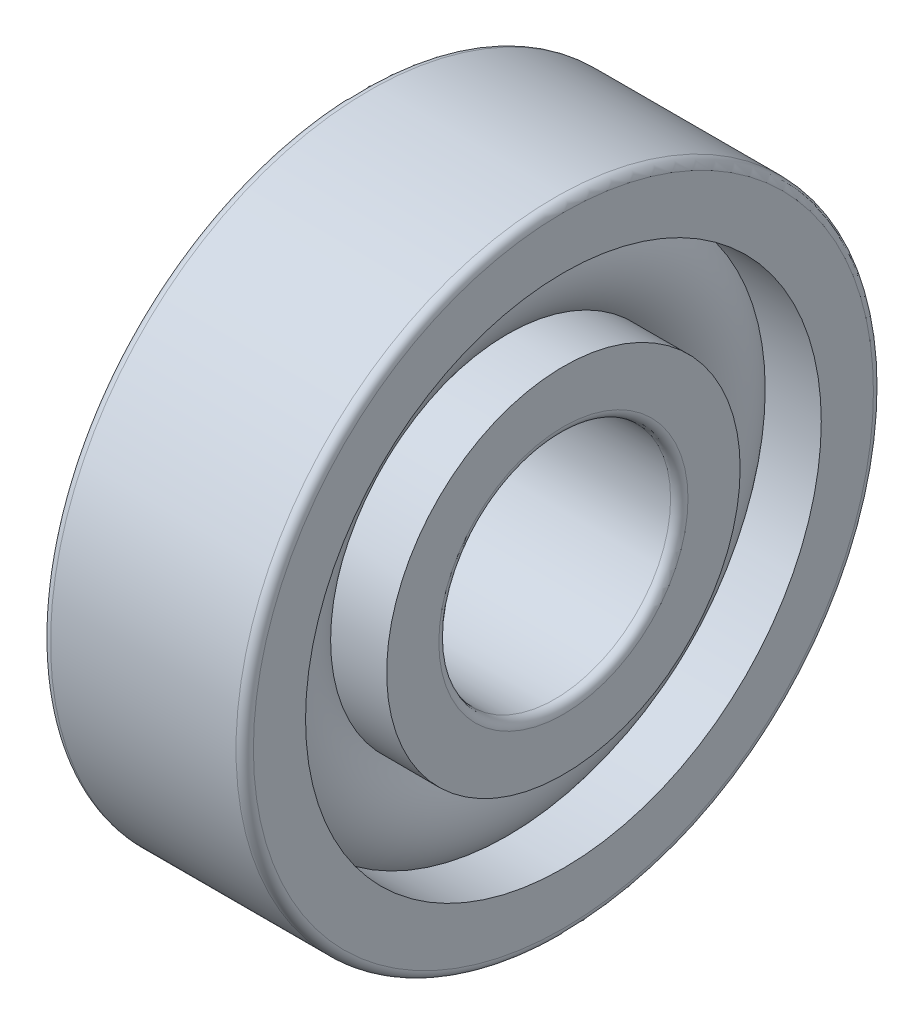
SolidWorks part; units mm, degrees
ref_plane "Plane1" through (0, 0, 0) normal (0, 0, 1) x (1, 0, 0)
ref_plane "Plane2" through (0, 0, 0) normal (0, 1, 0) x (1, 0, 0)
ref_plane "Plane3" through (0, 0, 0) normal (1, 0, 0) x (0, 0, -1)
other "Configuration Table"
sketch "Clipboard" plane through (0, 0, 0) normal (0, 0, 1) x (1, 0, 0)
  line L0 (-10, 0) -> (10, 0) construction
  line L1 (0, 0) -> (22.3471, -0.7804)
  line L2 (0, 0) -> (7.4954, 0.2617)
  line L3 (0, 0) -> (22.3471, -0.7804)
  line L4 (0, 0) -> (-22.3573, -0.3902)
  dimension "BallCLRad" = 7.5
  dimension "Count" = 2
sketch "CagSpiSke" plane through (0, 0, 0) normal (0, 0, 1) x (1, 0, 0)
  line L0 (0.21, 7.15) -> (0.21, 7.85)
  line L1 (0.21, 7.85) -> (-0.21, 7.85)
  line L2 (-0.21, 7.85) -> (-0.21, 7.15)
  line L3 (-0.21, 7.15) -> (0.21, 7.15)
  line L4 (-20.6375, 0) -> (20.6375, 0) construction
  line L5 (0, 0) -> (0, 23.7692) construction
  dimension "OD" = 15.7
  dimension "ID" = 14.3
revolve "CageSpine" add sketch "CagSpiSke" angle 0.001 about L4 reverse direction yes
ref_axis "Axis1" through (-50, 0, 0) along (1, 0, 0)
sketch "CagBalSke" plane through (0, 0, 0) normal (0, 0, 1) x (1, 0, 0)
  line L0 (-2.31, 7.5) -> (2.31, 7.5)
  line L1 (-1.905, 7.5) -> (1.905, 7.5) construction
  line L2 (-10, 0) -> (10, 0) construction
  line L3 (0, 0) -> (0, 24) construction
  arc A0 (2.31, 7.5) -> (-2.31, 7.5) centre (0, 7.5) cw
  dimension "BallCLRad" = 7.5
revolve "CageBall" [suppressed] add sketch "CagBalSke" angle 360 about L1 reverse direction yes
pattern_circular "CageBalls" [suppressed] count 2 every 180 about axis through (-50, 0, 0) along (1, 0, 0)
sketch "CagTrmODSke" plane through (0, 0, 0) normal (0, 0, 1) x (1, 0, 0)
  line L0 (2.311, 7.85) -> (2.311, 9.811)
  line L1 (2.311, 9.811) -> (-2.311, 9.811)
  line L2 (-2.311, 9.811) -> (-2.311, 7.85)
  line L3 (-2.311, 7.85) -> (2.311, 7.85)
  line L4 (-20.6375, 0) -> (20.6375, 0) construction
  line L5 (0, 0) -> (0, 25) construction
  dimension "Width" = 4.622
  dimension "ID" = 15.7
  dimension "OD" = 19.622
revolve "CageTrimOD" [suppressed] cut sketch "CagTrmODSke" angle 360 about L4 reverse direction yes
sketch "CagTrmIDSke" plane through (0, 0, 0) normal (0, 0, 1) x (1, 0, 0)
  line L0 (2.311, 5.191) -> (2.311, 7.15)
  line L1 (2.311, 7.15) -> (-2.311, 7.15)
  line L2 (-2.311, 7.15) -> (-2.311, 5.191)
  line L3 (-2.311, 5.191) -> (2.311, 5.191)
  line L4 (-20.6375, 0) -> (20.6375, 0) construction
  line L5 (0, 0) -> (0, 25) construction
  dimension "Width" = 4.622
  dimension "ID" = 10.382
  dimension "OD" = 14.3
revolve "CageTrimID" [suppressed] cut sketch "CagTrmIDSke" angle 360 about L4 reverse direction yes
sketch "BalSimSke" plane through (0, 0, 0) normal (0, 0, 1) x (1, 0, 0)
  line L0 (-10, 0) -> (10, 0) construction
  line L1 (-10, 7.5) -> (10, 7.5) construction
  line L2 (0, 0) -> (0, 23) construction
  circle A0 centre (0, 7.5) radius 2.1
  dimension "BallCLRad" = 7.5
revolve "BallsSimplified" add sketch "BalSimSke" angle 360 about L0
sketch "BalDetSke" plane through (0, 0, 0) normal (0, 0, 1) x (1, 0, 0)
  line L0 (-2.1, 7.5) -> (2.1, 7.5)
  line L1 (-1.905, 7.5) -> (1.905, 7.5) construction
  line L2 (0, 0) -> (0, 25) construction
  arc A0 (2.1, 7.5) -> (-2.1, 7.5) centre (0, 7.5) cw
  dimension "BallCLRad" = 7.5
revolve "BallDetailed" [suppressed] add sketch "BalDetSke" angle 360 about L1 reverse direction yes
sketch "InnRacSke" plane through (0, 0, 0) normal (0, 0, 1) x (1, 0, 0)
  line L0 (-1.5315, 6.1) -> (-3.5, 6.1)
  line L1 (-3.5, 6.1) -> (-3.5, 4.3)
  line L2 (-3.2, 4) -> (3.2, 4)
  line L3 (3.5, 4.3) -> (3.5, 6.1)
  line L4 (3.5, 6.1) -> (1.5315, 6.1)
  line L5 (-20.6375, 0) -> (20.6375, 0) construction
  line L6 (0, 0) -> (0, 30) construction
  arc A0 (-3.5, 4.3) -> (-3.2, 4) centre (-3.2, 4.3) ccw
  arc A1 (3.2, 4) -> (3.5, 4.3) centre (3.2, 4.3) ccw
  arc A2 (1.5315, 6.1) -> (-1.5315, 6.1) centre (0, 7.5) cw
  dimension "BallCLRad" = 7.5
  dimension "Fillet_radius" = 0.3
  dimension "Ball_diameter" = 4.15
  dimension "ID" = 8
  dimension "OD" = 12.2
  dimension "Width" = 7
revolve "InnerRace" add sketch "InnRacSke" angle 360 about L5 reverse direction yes
sketch "OutRacSke" plane through (0, 0, 0) normal (0, 0, 1) x (1, 0, 0)
  line L0 (-1.5315, 8.9) -> (-3.5, 8.9)
  line L1 (-3.5, 8.9) -> (-3.5, 10.7)
  line L2 (-3.2, 11) -> (3.2, 11)
  line L3 (3.5, 10.7) -> (3.5, 8.9)
  line L4 (3.5, 8.9) -> (1.5315, 8.9)
  line L5 (-20.6375, 0) -> (20.6375, 0) construction
  line L6 (0, 0) -> (0, 30) construction
  arc A0 (-3.5, 10.7) -> (-3.2, 11) centre (-3.2, 10.7) cw
  arc A1 (3.2, 11) -> (3.5, 10.7) centre (3.2, 10.7) cw
  arc A2 (1.5315, 8.9) -> (-1.5315, 8.9) centre (0, 7.5) ccw
  dimension "BallCLRad" = 7.5
  dimension "Fillet_radius" = 0.3
  dimension "Ball_diameter" = 4.15
  dimension "Width" = 7
revolve "OuterRace" add sketch "OutRacSke" angle 360 about L5 reverse direction yes
pattern_circular "BallsDetailed" [suppressed] count 2 every 180 about axis through (-50, 0, 0) along (1, 0, 0)
equation "\"BallCLRad@Clipboard\" = ( \"OD@OutRacSke\" + \"ID@InnRacSke\" ) / 4"
equation "\"BallCLRad@BalSimSke\" = \"BallCLRad@Clipboard\""
equation "\"BallCLRad@BalDetSke\" = \"BallCLRad@Clipboard\""
equation "\"BallCLRad@InnRacSke\" = \"BallCLRad@Clipboard\""
equation "\"BallCLRad@OutRacSke\" = \"BallCLRad@Clipboard\""
equation "\"Ball_diameter@InnRacSke\" = \"Ball_diameter@BalDetSke\" - 0.05"
equation "\"Ball_diameter@OutRacSke\" = \"Ball_diameter@BalDetSke\" - 0.05"
equation "\"Ball_diameter@BalSimSke\" = \"Ball_diameter@BalDetSke\""
equation "\"Width@OutRacSke\" = \"Width@InnRacSke\""
equation "\"Fillet_radius@OutRacSke\" = \"Fillet_radius@InnRacSke\""
equation "\"Max_count@Clipboard\" = int( 3.14159265 / atn(( \"Ball_diameter@BalDetSke\" / 2) / sqr( \"BallCLRad@Clipboard\"  *  \"BallCLRad@Clipboard\" - ( \"Ball_diameter@BalDetSke\" / 2) *  ( \"Ball_diameter@BalDetSke\" / 2))))"
equation "\"Max_count@Clipboard\" = ((sgn( \"Max_count@Clipboard\" - \"Count@Clipboard\" )-1)*( \"Max_count@Clipboard\" - \"Count@Clipboard\" ))/-2+ \"Count@Clipboard\""
equation "\"Count@BallsDetailed\" = int( \"Show_count@Clipboard\" ) "
equation "\"Count@BallsDetailed\" = ((sgn( \"Count@BallsDetailed\" - \"Max_count@Clipboard\" )-1)*( \"Count@BallsDetailed\" - \"Max_count@Clipboard\" ))/-2+ \"Max_count@Clipboard\""
equation "\"Count@BallsDetailed\" = ((sgn( \"Count@BallsDetailed\" - \"Min_count@Clipboard\" )+1)*( \"Count@BallsDetailed\" - \"Min_count@Clipboard\"))/2 +\"Min_count@Clipboard\""
equation "\"Angle@BallsDetailed\" = 360.0 / \"Max_count@Clipboard\""
equation "\"BallCLRad@CagBalSke\" = \"BallCLRad@Clipboard\""
equation "\"Count@CageBalls\" = \"Count@BallsDetailed\""
equation "\"Angle@CageBalls\" = \"Angle@BallsDetailed\""
equation "\"Angle@CageSpine\" =  \"Angle@CageBalls\" * ( \"Count@CageBalls\" -1 + int( \"Count@CageBalls\" / \"Max_count@Clipboard\" ) )  + 0.001 -  int( \"Count@CageBalls\" / \"Max_count@Clipboard\" ) * 0.001"
equation "\"Angle@CageSpine\" =  \"Angle@CageSpine\" * int( \"Min_count@Clipboard\" / 2) + int(1 / \"Min_count@Clipboard\")  * 0.001"
equation "\"CageWallOD@CagBalSke\" =  \"Ball_diameter@BalDetSke\" * 1.1"
equation "\"Thickness@CagSpiSke\" =  \"Ball_diameter@BalDetSke\" * 0.1"
equation "\"OD@CagTrmODSke\" = \"BallCLRad@Clipboard\" * 2 + \"CageWallOD@CagBalSke\" + 0.002"
equation "\"ID@CagTrmODSke\" = \"BallCLRad@Clipboard\" * 2 + \"Ball_diameter@BalDetSke\" / 6"
equation "\"OD@CagTrmIDSke\" = \"BallCLRad@Clipboard\" * 2 - \"Ball_diameter@BalDetSke\" / 6"
equation "\"ID@CagTrmIDSke\" = \"BallCLRad@Clipboard\" * 2 - \"CageWallOD@CagBalSke\" + 0.002"
equation "\"OD@CagSpiSke\" = \"ID@CagTrmODSke\""
equation "\"ID@CagSpiSke\" = \"OD@CagTrmIDSke\""
equation "\"Width@CagTrmODSke\" = \"CageWallOD@CagBalSke\" + 0.002"
equation "\"Width@CagTrmIDSke\" = \"CageWallOD@CagBalSke\" + 0.002"
